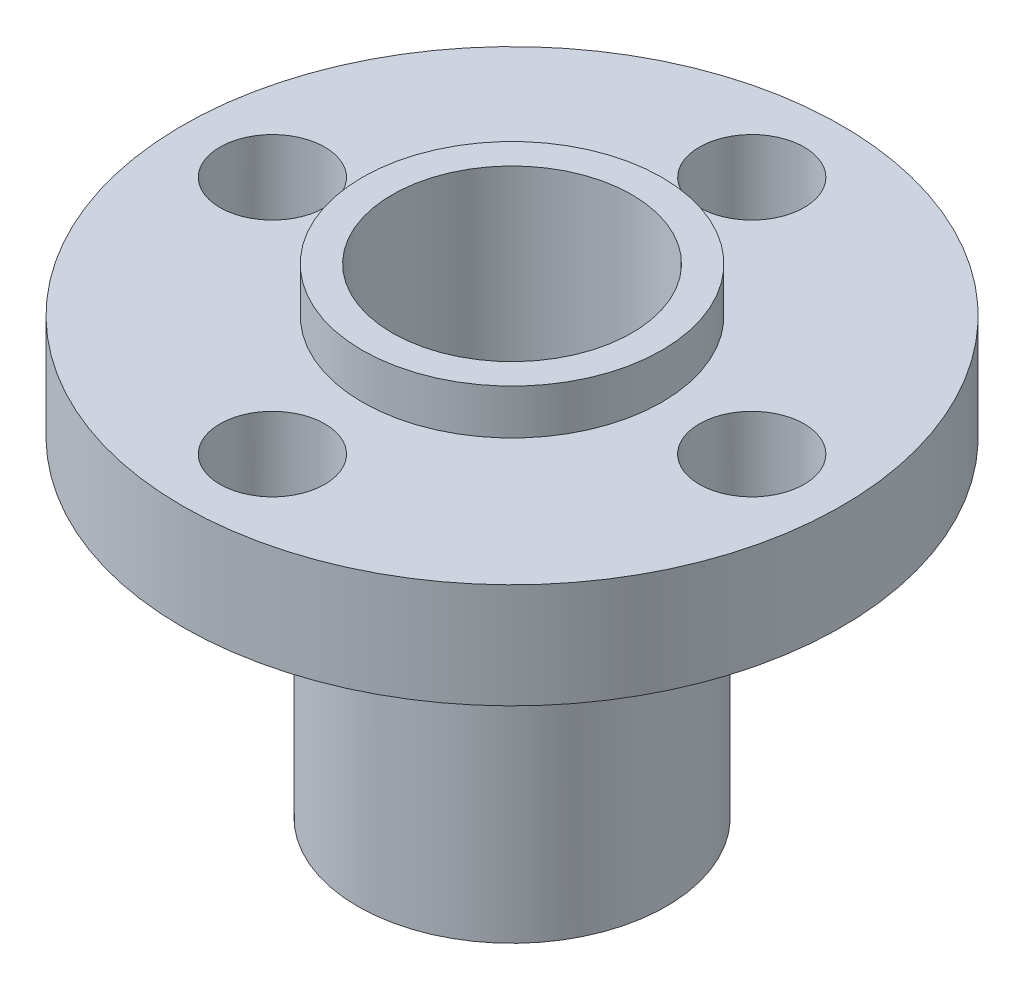
SolidWorks part; units mm, degrees
ref_plane "前视基准面" through (0, 0, 0) normal (0, 0, 1) x (1, 0, 0)
ref_plane "上视基准面" through (0, 0, 0) normal (0, 1, 0) x (1, 0, 0)
ref_plane "右视基准面" through (0, 0, 0) normal (1, 0, 0) x (0, 0, -1)
sketch "草图1" plane through (0, 0, 0) normal (0, 1, 0) x (1, 0, 0)
  circle A0 centre (0, 0) radius 4
  circle A1 centre (0, 0) radius 8 construction
  circle A2 centre (0, 0) radius 11
  circle A3 centre (0, 0) radius 5.15
  dimension "D1" = 10.3
  dimension "D2" = 16
  dimension "D3" = 22
  dimension "D4" = 8
extrude "凸台-拉伸2" add sketch "草图1" along normal blind 3.5 contours A2
sketch "草图2" plane through (0, 0, 0) normal (0, -1, 0) x (1, 0, 0)
  circle A0 centre (0, 0) radius 5.15
  dimension "D1" = 10.3
extrude "凸台-拉伸3" add sketch "草图2" along normal blind 11
sketch "草图3" plane through (0, -11, 0) normal (0, -1, 0) x (1, 0, 0)
  circle A0 centre (0, 0) radius 4
  dimension "D1" = 8
extrude "切除-拉伸1" cut sketch "草图3" against normal through all both and the other way through all
sketch "草图4" plane through (0, 3.5, 0) normal (0, 1, 0) x (1, 0, 0)
  circle A0 centre (0, 0) radius 8 construction
  circle A1 centre (0, 8) radius 1.75
  dimension "D1" = 16
  dimension "D2" = 3.5
extrude "切除-拉伸4" cut sketch "草图4" against normal up to next contours A1
pattern_circular "阵列(圆周)6" count 4 over 360 about axis through (0, 3.5, 0) along (0, -1, 0) of "切除-拉伸4"
sketch "草图6" plane through (0, 0, 0) normal (0, 1, 0) x (1, 0, 0)
  line L0 (0, -11) -> (0, 11) construction
  circle A0 centre (0, 0) radius 11 construction
sketch "草图7" plane through (0, 3.5, 0) normal (0, 1, 0) x (1, 0, 0)
  line L0 (0, -11) -> (0, 11) construction
  circle A0 centre (0, 0) radius 5
  dimension "D1" = 10
extrude "凸台-拉伸4" add sketch "草图7" along normal blind 1.5
sketch "草图8" plane through (0, 5, 0) normal (0, 1, 0) x (1, 0, 0)
  line L0 (0, -11) -> (0, 11) construction
  circle A0 centre (0, 0) radius 4
  dimension "D1" = 8
extrude "切除-拉伸5" cut sketch "草图8" against normal through all
